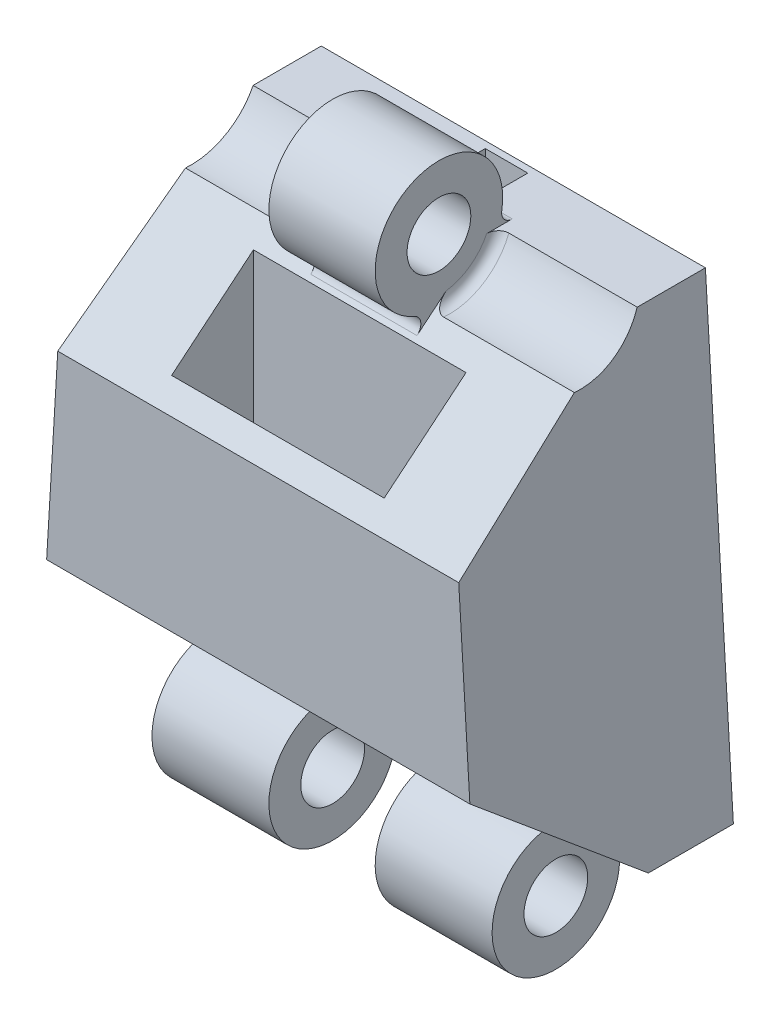
SolidWorks part; units mm, degrees
ref_plane "Front Plane" through (0, 0, 0) normal (0, 0, 1) x (1, 0, 0)
ref_plane "Top Plane" through (0, 0, 0) normal (0, 1, 0) x (1, 0, 0)
ref_plane "Right Plane" through (0, 0, 0) normal (1, 0, 0) x (0, 0, -1)
sketch "Sketch1" plane through (0, 0, 0) normal (0, 0, 1) x (1, 0, 0)
  line L0 (-56.5743, 0) -> (-35.8731, 0)
  line L1 (-55.2587, 22) -> (-37.1887, 22)
  line L2 (-56.5743, 0) -> (-55.2587, 22)
  line L3 (-35.8731, 0) -> (-37.1887, 22)
extrude "Boss-Extrude1" add sketch "Sketch1" along normal blind 12
sketch "Sketch2" plane through (0, 0, 12) normal (0, 0, 1) x (1, 0, 0)
  line L0 (-35.8731, 0) -> (-56.5743, 0)
  line L1 (-46.2237, 0) -> (-46.2237, 29.5391)
ref_plane "Plane1" through (-46.2237, 0, 0) normal (1, 0, 0) x (0, 0, -1)
sketch "Sketch3" plane through (-46.2237, 0, 0) normal (1, 0, 0) x (0, 0, -1)
  line L0 (0, 0) -> (-4, 0)
  line L1 (-12, 0) -> (0, 0) construction
  line L2 (-4, 0) -> (-12, 6.614)
  line L3 (-12, 0) -> (-12, 22) construction
  line L4 (-12, 6.614) -> (-12, 0)
  line L5 (-12, 0) -> (-4, 0)
extrude "Cut-Extrude1" cut sketch "Sketch3" against normal through all both and the other way through all contours L4 L5 L2 region at (-46.2237, 2.2047, 9.3333)
sketch "Sketch6" plane through (-46.2237, 0, 0) normal (1, 0, 0) x (0, 0, -1)
  line L1 (0, 0) -> (-12, 0)
  line L2 (-6, 0) -> (-6, -1.1)
  circle A0 centre (-6, -1.1) radius 1.5
  circle A1 centre (-6, -1.1) radius 3
extrude "Boss-Extrude2" add sketch "Sketch6" along normal mid plane 16 contours L1 A1 A0 | L1 A1 A0 region at (-46.2237, -0.5537, 3.1241) region at (-46.2237, 0.8343, 6)
extrude "Cut-Extrude2" cut sketch "Sketch6<3>" against normal mid plane 5 contours L1 A1 A0 | L1 A1 A0 region at (-46.2237, -0.5537, 3.1241) region at (-46.2237, 0.8343, 6)
sketch "Sketch6<3>" plane through (-46.2237, 0, 0) normal (1, 0, 0) x (0, 0, -1) same geometry as "Sketch6"
sketch "Sketch8" plane through (-46.2237, 0, 0) normal (1, 0, 0) x (0, 0, -1)
  line L0 (0, 22) -> (-4, 22)
  line L1 (-12, 22) -> (0, 22) construction
  line L2 (-4, 22) -> (-12, 15.3704)
  line L3 (-12, 6.614) -> (-12, 22) construction
  line L4 (-12, 15.3704) -> (-12, 22)
  line L5 (-12, 22) -> (-4, 22)
extrude "Cut-Extrude3" cut sketch "Sketch8" against normal through all both and the other way through all contours L5 L4 L2 region at (-46.2237, 19.7901, 9.3333)
sketch "Sketch9" plane through (-46.2237, 0, 0) normal (1, 0, 0) x (0, 0, -1)
  line L0 (-12, 15.3704) -> (-12, 26.5168)
  line L1 (0, 22) -> (-12, 22)
  line L2 (-6, 22) -> (-6, 23.1)
  circle A0 centre (-6, 23.1) radius 1.5
  circle A1 centre (-6, 23.1) radius 3
extrude "Boss-Extrude3" add sketch "Sketch9" along normal mid plane 5 contours L1 A1 A0 | L1 A1 A0 region at (-46.2237, 21.1657, 6) region at (-46.2237, 22.0727, 4.0946)
sketch "Sketch11" plane through (-43.7237, 0, 0) normal (1, 0, 0) x (0, 0, -1)
  circle A0 centre (-6, 23.1) radius 3
extrude "Cut-Extrude4" cut sketch "Sketch11" along normal blind 10
sketch "Sketch12" plane through (-48.7237, 0, 0) normal (-1, 0, 0) x (0, 0, 1)
  circle A0 centre (6, 23.1) radius 3
extrude "Cut-Extrude5" cut sketch "Sketch12" along normal blind 10
fillet "Fillet1" radius 0.5 2 edges at (-46.2237, 22, 3.2089) (-46.2237, 20.1128, 6.2772)
fillet "Fillet2" radius 0.5 2 edges at (-48.7237, 20.5446, 4.4283) (-43.7237, 20.5446, 4.4283)
sketch "Sketch13" plane through (0, 15.008, 12.4372) normal (0, 0.77, 0.6381) x (1, 0, 0)
  line L0 (-46.2237, 0.5678) -> (-46.2237, 1.7678)
  line L1 (-55.6551, 0.5678) -> (-36.7922, 0.5678) construction
  line L2 (-41.2237, 1.7678) -> (-41.2237, 6.7678)
  line L4 (-51.2237, 1.7678) -> (-41.2237, 1.7678)
  line L5 (-41.2237, 6.7678) -> (-51.2237, 6.7678)
  line L6 (-51.2237, 6.7678) -> (-51.2237, 1.7678)
  point P11 (-46.2237, 1.7678)
ref_plane "Plane2" through (0, 10, 0) normal (0, 1, 0) x (1, 0, 0)
sketch "Sketch14" plane through (0, 10, 0) normal (0, 1, 0) x (1, 0, 0)
  line L0 (-51.2237, -7.2262) -> (-51.2237, -11.076)
  line L1 (-51.2237, -11.076) -> (-41.2237, -11.076)
  line L2 (-41.2237, -11.076) -> (-41.2237, -7.2262)
  line L3 (-41.2237, -7.2262) -> (-51.2237, -7.2262)
extrude "Cut-Extrude6" cut sketch "Sketch14" against normal up to surface and the other way up to surface up to face at (-46.2237, 2.0775, 6.5128) other way up to face at (-46.2124, 19.1095, 7.4879)
sketch "Sketch15" plane through (-46.2237, 0, 0) normal (1, 0, 0) x (0, 0, -1)
  line L0 (-0.32, 0) -> (-2.32, 0)
  line L1 (-4, 0) -> (0, 0) construction
  line L2 (-2.32, 0) -> (-2.32, 0.3356)
  line L4 (-0.32, 0.3356) -> (-0.32, 0)
  line L5 (-0.32, 0.3356) -> (-0.32, 22)
  line L6 (-3.2089, 22) -> (0, 22) construction
  line L7 (-0.32, 22) -> (-2.32, 22)
  line L8 (-2.32, 22) -> (-2.32, 0.3356)
extrude "Cut-Extrude7" cut sketch "Sketch15" against normal mid plane 2
